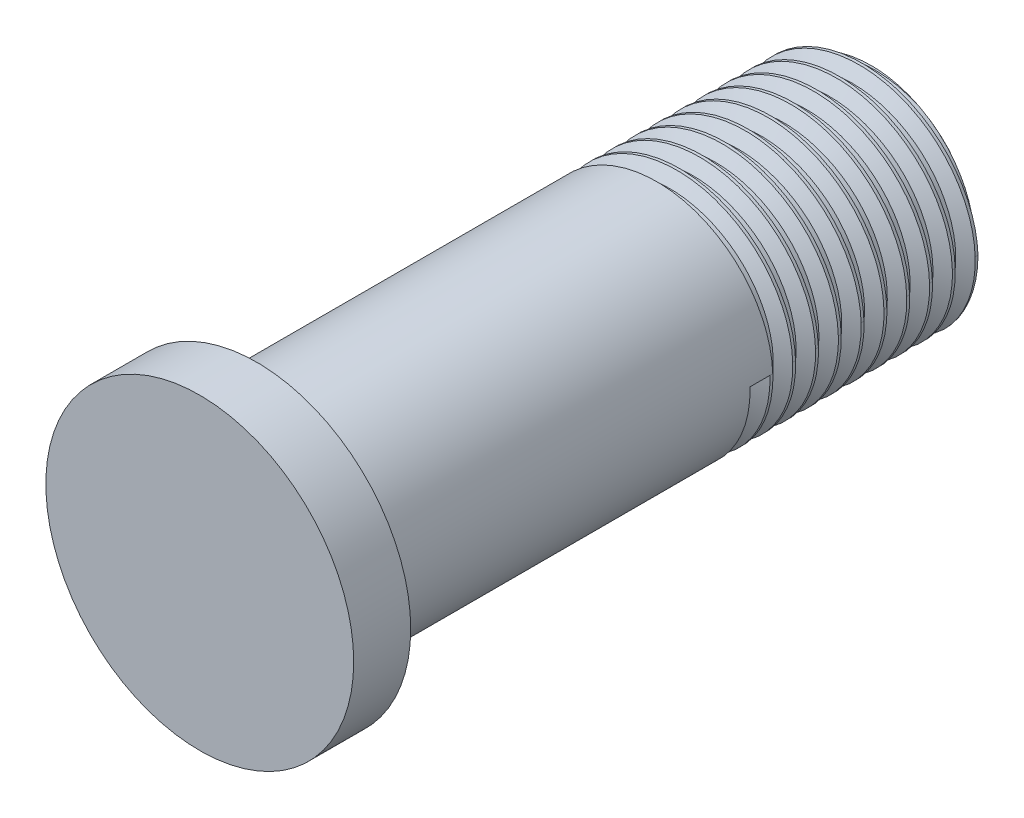
SolidWorks part; units mm, degrees
ref_plane "Спереди" through (0, 0, 0) normal (0, 0, 1) x (1, 0, 0)
ref_plane "Сверху" through (0, 0, 0) normal (0, 1, 0) x (1, 0, 0)
ref_plane "Справа" through (0, 0, 0) normal (1, 0, 0) x (0, 0, -1)
sketch "Эскиз1" plane through (0, 0, 0) normal (0, 0, 1) x (1, 0, 0)
  circle A0 centre (0, 0) radius 10
  dimension "D1" = 20
extrude "Бобышка-Вытянуть1" add sketch "Эскиз1" along normal mid plane 60
thread "Резьба1" pitch 2 method cut profile "Профиль резьбы1" start angle 0, offset 0, length 20, pitch 2, diameter 20
ref_plane "Плоскость4" through (10, 0, -30) normal (0, -1, 0) x (1, 0, 0)
sketch "Профиль резьбы1" plane through (10, 0, -30) normal (0, -1, 0) x (1, 0, 0)
  line L0 (0, 0) -> (0, 2) construction
  line L11 (0, 0) -> (0, 1.75)
  line L12 (0, 1.75) -> (-1.0825, 1.125)
  line L13 (-1.0825, 1.125) -> (-1.0825, 0.625)
  line L15 (-1.0825, 0.625) -> (0, 0)
  line L17 (-1.0825, 0.875) -> (0, 0.875) construction
  point P2 (0, 0)
  dimension "Pitch" = 2
  dimension "Profile_Angle" = 60
  dimension "Profile_Land" = 0.5
  dimension "Profile_Height" = 1.0825
sketch "Эскиз10" plane through (0, 0, 30) normal (0, 0, 1) x (1, 0, 0)
  circle A0 centre (0, 0) radius 13.5
  dimension "D1" = 27
extrude "Бобышка-Вытянуть2" add sketch "Эскиз10" against normal blind 5
sketch "Эскиз11" plane through (0, 0, 0) normal (0, 1, 0) x (1, 0, 0)
  line L0 (0, -1000) -> (0, 49000) construction
  line L1 (10, 30) -> (10, 28.25)
  line L2 (10, 28.25) -> (7.5633, 30)
  line L3 (10, 30) -> (-10, 30) construction
  line L4 (7.5633, 30) -> (10, 30)
  dimension "D1" = 3
revolve "Вырез-Повернуть1" cut sketch "Эскиз11" angle 360 about L0
